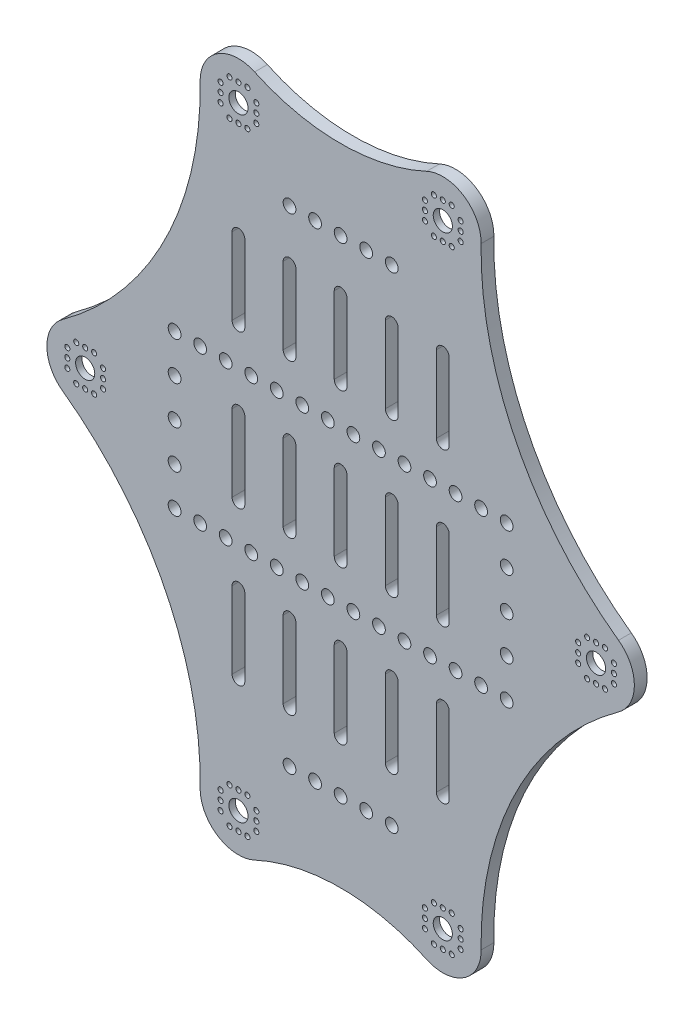
SolidWorks part; units mm, degrees
ref_plane "前视基准面" through (0, 0, 0) normal (0, 0, 1) x (1, 0, 0)
ref_plane "上视基准面" through (0, 0, 0) normal (0, 1, 0) x (1, 0, 0)
ref_plane "右视基准面" through (0, 0, 0) normal (1, 0, 0) x (0, 0, -1)
other "Configuration Table"
sketch "Sketch1" plane through (0, 0, 0) normal (0, 0, 1) x (1, 0, 0)
  line L0 (0, 0) -> (0, 120) construction
  line L1 (0, 120) -> (40, 120) construction
  line L2 (0, 0) -> (100, 0) construction
  circle A1 centre (100, 0) radius 15
  circle A2 centre (40, 120) radius 15
  circle A3 centre (-100, 0) radius 15
  circle A4 centre (-40, 120) radius 15
  circle A5 centre (40, -120) radius 15
  circle A6 centre (-40, -120) radius 15
  arc A7 (-33.6842, 133.6055) -> (33.6842, 133.6055) centre (0, 206.1684) ccw
  arc A8 (-33.6842, -133.6055) -> (33.6842, -133.6055) centre (0, -206.1684) cw
  arc A9 (-108.7909, 12.154) -> (-54.9978, 119.7403) centre (-184.9783, 117.4891) ccw
  arc A10 (108.7909, 12.154) -> (54.9978, 119.7403) centre (184.9783, 117.4891) cw
  arc A11 (108.7909, -12.154) -> (54.9978, -119.7403) centre (184.9783, -117.4891) ccw
  arc A12 (-108.7909, -12.154) -> (-54.9978, -119.7403) centre (-184.9783, -117.4891) cw
  dimension "D1" = 30
  dimension "D2" = 30
  dimension "D6" = 80
  dimension "D7" = 130
  dimension "D3" = 40
  dimension "D4" = 100
  dimension "D5" = 120
extrude "Boss-Extrude1" add sketch "Sketch1" along normal blind 5 contours A3 A12 A6 A8 A5 A11 A1 A10 A2 A7 A4 A9 | A3 | A4 | A2 | A1 | A5 | A6 A7 region at (100, 0, 0) region at (0, 0, 0) region at (40, 120, 0) region at (40, -120, 0) region at (-40, 120, 0) region at (-40, -120, 0) region at (-100, 0, 0)
sketch "Sketch2" plane through (0, 0, 0) normal (0, 0, -1) x (-1, 0, 0)
  line L0 (0, 0) -> (0, 91.5521) construction
  line L1 (0, 0) -> (39.9574, 0) construction
  circle A0 centre (-40, 120) radius 11.25
  circle A1 centre (-100, 0) radius 11.25
  circle A2 centre (100, 0) radius 11.25
  circle A3 centre (40, 120) radius 11.25
  circle A4 centre (40, -120) radius 11.25
  circle A5 centre (-40, -120) radius 11.25
  dimension "D1" = 22.5
extrude "Cut-Extrude1" cut sketch "Sketch2" against normal blind 2.5
sketch "Sketch3" plane through (0, 0, 2.5) normal (0, 0, -1) x (-1, 0, 0)
  line L0 (-40, 120) -> (-40, 127) construction
  line L1 (-40, 127) -> (-36.5, 127) construction
  line L2 (-100, 0) -> (-100, 7) construction
  line L3 (-100, 7) -> (-96.5, 7) construction
  circle A0 centre (-40, 120) radius 3.75
  circle A1 centre (-40, 127) radius 1
  circle A2 centre (-36.5, 127) radius 1
  circle A3 centre (-43.5, 127) radius 1
  circle A4 centre (-40, 120) radius 3.75
  circle A5 centre (-33, 123.5) radius 1
  circle A6 centre (-33, 120) radius 1
  circle A7 centre (-33, 116.5) radius 1
  circle A8 centre (-40, 120) radius 3.75
  circle A9 centre (-36.5, 113) radius 1
  circle A10 centre (-40, 113) radius 1
  circle A11 centre (-43.5, 113) radius 1
  circle A12 centre (-40, 120) radius 3.75
  circle A13 centre (-47, 116.5) radius 1
  circle A14 centre (-47, 120) radius 1
  circle A15 centre (-47, 123.5) radius 1
  circle A16 centre (-100, 0) radius 3.75
  circle A17 centre (-100, 7) radius 1
  circle A18 centre (-96.5, 7) radius 1
  circle A19 centre (-103.5, 7) radius 1
  circle A41 centre (-100, 0) radius 3.75
  circle A42 centre (-93, 3.5) radius 1
  circle A43 centre (-93, 0) radius 1
  circle A44 centre (-93, -3.5) radius 1
  circle A45 centre (-100, 0) radius 3.75
  circle A46 centre (-96.5, -7) radius 1
  circle A47 centre (-100, -7) radius 1
  circle A48 centre (-103.5, -7) radius 1
  circle A49 centre (-100, 0) radius 3.75
  circle A50 centre (-107, -3.5) radius 1
  circle A51 centre (-107, 0) radius 1
  circle A52 centre (-107, 3.5) radius 1
  point P33 (-40, 120)
  point P63 (-100, 0)
  dimension "D1" = 7.5
  dimension "D2" = 2
  dimension "D4" = 2
  dimension "D7" = 7.5
  dimension "D8" = 2
  dimension "D10" = 2
  dimension "D3" = 7
  dimension "D5" = 3.5
  dimension "D9" = 7
  dimension "D11" = 3.5
  dimension "D12" = 4
  dimension "D6" = 4
extrude "Cut-Extrude2" cut sketch "Sketch3" against normal blind 2.5 contours A15 | A14 | A13 | A0 | A11 | A10 | A9 | A7 | A6 | A5 | A2 | A1 | A3 | A47 | A49 | A43 | A45 | A16 | A50 | A51 | A52 | A19 | A17 | A18 | A46 | A48 | A44 | A42
mirror "Mirror1" about plane through (0, 0, 0) normal (1, 0, 0) of "Cut-Extrude2"
mirror "Mirror2" about plane through (0, 0, 0) normal (0, 1, 0) of "Cut-Extrude2", "Mirror1"
sketch "Sketch4" plane through (0, 0, 5) normal (0, 0, 1) x (1, 0, 0)
  arc A24 (-83.8778, 0) -> (-30.4292, 105.6743) centre (-184.9783, 117.4891) ccw
  arc A25 (-30.4292, -105.6743) -> (-83.8778, 0) centre (-184.9783, -117.4891) ccw
  arc A26 (30.4292, -105.6743) -> (-30.4292, -105.6743) centre (0, -206.1684) ccw
  arc A27 (83.8778, 0) -> (30.4292, -105.6743) centre (184.9783, -117.4891) ccw
  arc A28 (30.4292, 105.6743) -> (83.8778, 0) centre (184.9783, 117.4891) ccw
  arc A29 (-30.4292, 105.6743) -> (30.4292, 105.6743) centre (0, 206.1684) ccw
  arc A30 (-83.8778, 0) -> (-30.4292, 105.6743) centre (-184.9783, 117.4891) ccw
  arc A31 (-30.4292, -105.6743) -> (-83.8778, 0) centre (-184.9783, -117.4891) ccw
  arc A32 (30.4292, -105.6743) -> (-30.4292, -105.6743) centre (0, -206.1684) ccw
  arc A33 (83.8778, 0) -> (30.4292, -105.6743) centre (184.9783, -117.4891) ccw
  arc A34 (30.4292, 105.6743) -> (83.8778, 0) centre (184.9783, 117.4891) ccw
  arc A35 (-30.4292, 105.6743) -> (30.4292, 105.6743) centre (0, 206.1684) ccw
  dimension "D1" = 25
extrude "Cut-Extrude3" [suppressed] cut sketch "Sketch4" against normal through all
fillet "Fillet1" [suppressed] radius 20
sketch "Sketch5" plane through (0, 0, 0) normal (0, 0, -1) x (-1, 0, 0)
  line L0 (0, 95) -> (0, 126.1684) construction
  line L1 (0, 95) -> (20, 95) construction
  line L2 (0, -95) -> (0, -126.1684) construction
  line L3 (0, 0) -> (50.0339, 0) construction
  line L5 (0, -95) -> (20, -95) construction
  circle A0 centre (20, 95) radius 2.5
  circle A1 centre (0, 95) radius 2.5
  circle A2 centre (10, 95) radius 2.5
  circle A17 centre (10, -95) radius 2.5
  circle A18 centre (0, -95) radius 2.5
  circle A19 centre (20, -95) radius 2.5
  arc A20 (-33.6842, 133.6055) -> (33.6842, 133.6055) centre (0, 206.1684) ccw construction
  circle A21 centre (-20, 95) radius 2.5
  circle A22 centre (-10, 95) radius 2.5
  arc A23 (33.6842, -133.6055) -> (-33.6842, -133.6055) centre (0, -206.1684) ccw construction
  circle A24 centre (-20, -95) radius 2.5
  circle A25 centre (-10, -95) radius 2.5
  dimension "D1" = 5
  dimension "D2" = 5
  dimension "D4" = 5
  dimension "D3" = 95
  dimension "D5" = 10
extrude "Cut-Extrude4" cut sketch "Sketch5" against normal blind 12.5
sketch "Sketch7" [suppressed] plane through (0, 0, 0) normal (0, 0, -1) x (-1, 0, 0)
  line L0 (-142.3284, 63.1511) -> (-138.4501, 72.3684) construction
  line L1 (-66.361, 51.7375) -> (-44.32, 39.8221) construction
  line L2 (-152.9421, 69.9963) -> (-131.7148, 56.3059) construction
  line L3 (-131.7148, 56.3059) -> (-142.3284, 63.1511) construction
  line L4 (-55.3405, 45.7798) -> (-52.1848, 55.2688) construction
  circle A6 centre (-142.3284, 63.1511) radius 2.5
  circle A7 centre (-138.4501, 72.3684) radius 2.5
  circle A8 centre (-134.5717, 81.5857) radius 2.5
  circle A9 centre (-142.3284, 63.1511) radius 2.5
  circle A10 centre (-146.2068, 53.9338) radius 2.5
  circle A11 centre (-150.0851, 44.7165) radius 2.5
  arc A12 (-95.3356, 10.8708) -> (-54.9908, 100.526) centre (-184.9108, 105.0849) ccw construction
  arc A13 (-70.9715, 0) -> (-31.105, 85.8815) centre (-184.9108, 105.0849) ccw construction
  circle A14 centre (-55.3405, 45.7798) radius 2.5
  circle A15 centre (-52.1848, 55.2688) radius 2.5
  circle A16 centre (-48.3064, 64.4861) radius 2.5
  circle A17 centre (-59.2189, 36.5625) radius 2.5
  circle A18 centre (-63.0972, 27.3452) radius 2.5
  dimension "D1" = 5
  dimension "D2" = 5
  dimension "D7" = 5
  dimension "D9" = 5
  dimension "D3" = 100
  dimension "D4" = 10
  dimension "D5" = 10
  dimension "D6" = 10
  dimension "D8" = 100
  dimension "D10" = 10
  dimension "D11" = 2
extrude "Cut-Extrude5" [suppressed] cut sketch "Sketch7" against normal blind 10 contours A14 | A17 | A18 | A16 | A15
sketch "Sketch8" plane through (0, 0, 5) normal (0, 0, 1) x (1, 0, 0)
  line L0 (0, 0) -> (0, 75) construction
  line L1 (0, 75) -> (40, 75) construction
  line L2 (40, 75) -> (40, 45) construction
  line L3 (42.5, 75) -> (42.5, 45)
  line L4 (37.5, 75) -> (37.5, 45)
  line L5 (20, 75) -> (20, 45) construction
  line L6 (22.5, 75) -> (22.5, 45)
  line L7 (17.5, 75) -> (17.5, 45)
  line L8 (0, 75) -> (0, 45) construction
  line L9 (2.5, 75) -> (2.5, 45)
  line L10 (-2.5, 75) -> (-2.5, 45)
  line L11 (-20, 75) -> (-20, 45) construction
  line L12 (-17.5, 75) -> (-17.5, 45)
  line L13 (-22.5, 75) -> (-22.5, 45)
  line L14 (-40, 75) -> (-40, 45) construction
  line L15 (-37.5, 75) -> (-37.5, 45)
  line L16 (-42.5, 75) -> (-42.5, 45)
  line L17 (40, 120) -> (0, 120) construction
  line L18 (0, 15) -> (40, 15) construction
  line L19 (40, 15) -> (40, -15) construction
  line L20 (42.5, 15) -> (42.5, -15)
  line L21 (37.5, 15) -> (37.5, -15)
  line L22 (20, 15) -> (20, -15) construction
  line L23 (22.5, 15) -> (22.5, -15)
  line L24 (17.5, 15) -> (17.5, -15)
  line L25 (0, 15) -> (0, -15) construction
  line L26 (2.5, 15) -> (2.5, -15)
  line L27 (-2.5, 15) -> (-2.5, -15)
  line L28 (-20, 15) -> (-20, -15) construction
  line L29 (-17.5, 15) -> (-17.5, -15)
  line L30 (-22.5, 15) -> (-22.5, -15)
  line L31 (-40, 15) -> (-40, -15) construction
  line L32 (-37.5, 15) -> (-37.5, -15)
  line L33 (-42.5, 15) -> (-42.5, -15)
  line L34 (0, -45) -> (40, -45) construction
  line L35 (40, -45) -> (40, -75) construction
  line L36 (42.5, -45) -> (42.5, -75)
  line L37 (37.5, -45) -> (37.5, -75)
  line L38 (20, -45) -> (20, -75) construction
  line L39 (22.5, -45) -> (22.5, -75)
  line L40 (17.5, -45) -> (17.5, -75)
  line L41 (0, -45) -> (0, -75) construction
  line L42 (2.5, -45) -> (2.5, -75)
  line L43 (-2.5, -45) -> (-2.5, -75)
  line L44 (-20, -45) -> (-20, -75) construction
  line L45 (-17.5, -45) -> (-17.5, -75)
  line L46 (-22.5, -45) -> (-22.5, -75)
  line L47 (-40, -45) -> (-40, -75) construction
  line L48 (-37.5, -45) -> (-37.5, -75)
  line L49 (-42.5, -45) -> (-42.5, -75)
  arc A0 (42.5, 75) -> (37.5, 75) centre (40, 75) ccw
  arc A1 (37.5, 45) -> (42.5, 45) centre (40, 45) ccw
  arc A2 (22.5, 75) -> (17.5, 75) centre (20, 75) ccw
  arc A3 (17.5, 45) -> (22.5, 45) centre (20, 45) ccw
  arc A4 (2.5, 75) -> (-2.5, 75) centre (0, 75) ccw
  arc A5 (-2.5, 45) -> (2.5, 45) centre (0, 45) ccw
  arc A6 (-17.5, 75) -> (-22.5, 75) centre (-20, 75) ccw
  arc A7 (-22.5, 45) -> (-17.5, 45) centre (-20, 45) ccw
  arc A8 (-37.5, 75) -> (-42.5, 75) centre (-40, 75) ccw
  arc A9 (-42.5, 45) -> (-37.5, 45) centre (-40, 45) ccw
  arc A10 (42.5, 15) -> (37.5, 15) centre (40, 15) ccw
  arc A11 (37.5, -15) -> (42.5, -15) centre (40, -15) ccw
  arc A12 (22.5, 15) -> (17.5, 15) centre (20, 15) ccw
  arc A13 (17.5, -15) -> (22.5, -15) centre (20, -15) ccw
  arc A14 (2.5, 15) -> (-2.5, 15) centre (0, 15) ccw
  arc A15 (-2.5, -15) -> (2.5, -15) centre (0, -15) ccw
  arc A16 (-17.5, 15) -> (-22.5, 15) centre (-20, 15) ccw
  arc A17 (-22.5, -15) -> (-17.5, -15) centre (-20, -15) ccw
  arc A18 (-37.5, 15) -> (-42.5, 15) centre (-40, 15) ccw
  arc A19 (-42.5, -15) -> (-37.5, -15) centre (-40, -15) ccw
  arc A20 (42.5, -45) -> (37.5, -45) centre (40, -45) ccw
  arc A21 (37.5, -75) -> (42.5, -75) centre (40, -75) ccw
  arc A22 (22.5, -45) -> (17.5, -45) centre (20, -45) ccw
  arc A23 (17.5, -75) -> (22.5, -75) centre (20, -75) ccw
  arc A24 (2.5, -45) -> (-2.5, -45) centre (0, -45) ccw
  arc A25 (-2.5, -75) -> (2.5, -75) centre (0, -75) ccw
  arc A26 (-17.5, -45) -> (-22.5, -45) centre (-20, -45) ccw
  arc A27 (-22.5, -75) -> (-17.5, -75) centre (-20, -75) ccw
  arc A28 (-37.5, -45) -> (-42.5, -45) centre (-40, -45) ccw
  arc A29 (-42.5, -75) -> (-37.5, -75) centre (-40, -75) ccw
  point P3 (40, 60)
  point P11 (20, 60)
  point P18 (0, 60)
  point P25 (-20, 60)
  point P32 (-40, 60)
  point P44 (40, 0)
  point P51 (20, 0)
  point P58 (0, 0)
  point P65 (-20, 0)
  point P72 (-40, 0)
  point P80 (40, -60)
  point P87 (20, -60)
  point P94 (0, -60)
  point P101 (-20, -60)
  point P108 (-40, -60)
  dimension "D3" = 2.5
  dimension "D1" = 40
  dimension "D2" = 75
  dimension "D4" = 30
  dimension "D6" = 20
  dimension "D8" = 60
  dimension "D5" = 5
  dimension "D7" = 3
extrude "Cut-Extrude6" cut sketch "Sketch8" against normal blind 10
sketch "Sketch9" plane through (0, 0, 5) normal (0, 0, 1) x (1, 0, 0)
  line L0 (0, 0) -> (0, 30) construction
  line L1 (0, 30) -> (-65, 30) construction
  line L2 (0, 0) -> (100, 0) construction
  line L3 (0, -30) -> (-65, -30) construction
  circle A0 centre (-65, 30) radius 2.5
  circle A1 centre (-55, 30) radius 2.5
  circle A2 centre (-45, 30) radius 2.5
  circle A3 centre (-35, 30) radius 2.5
  circle A4 centre (-25, 30) radius 2.5
  circle A5 centre (-15, 30) radius 2.5
  circle A6 centre (-5, 30) radius 2.5
  circle A7 centre (5, 30) radius 2.5
  circle A8 centre (15, 30) radius 2.5
  circle A9 centre (25, 30) radius 2.5
  circle A10 centre (35, 30) radius 2.5
  circle A11 centre (45, 30) radius 2.5
  circle A12 centre (55, 30) radius 2.5
  circle A13 centre (65, 30) radius 2.5
  circle A14 centre (65, -30) radius 2.5
  circle A15 centre (55, -30) radius 2.5
  circle A16 centre (45, -30) radius 2.5
  circle A17 centre (35, -30) radius 2.5
  circle A18 centre (25, -30) radius 2.5
  circle A19 centre (15, -30) radius 2.5
  circle A20 centre (5, -30) radius 2.5
  circle A21 centre (-5, -30) radius 2.5
  circle A22 centre (-15, -30) radius 2.5
  circle A23 centre (-25, -30) radius 2.5
  circle A24 centre (-35, -30) radius 2.5
  circle A25 centre (-45, -30) radius 2.5
  circle A26 centre (-55, -30) radius 2.5
  circle A27 centre (-65, -30) radius 2.5
  dimension "D1" = 5
  dimension "D2" = 30
  dimension "D3" = 65
  dimension "D5" = 10
  dimension "D4" = 14
extrude "Cut-Extrude7" cut sketch "Sketch9" against normal blind 10
sketch "Sketch10" plane through (0, 0, 5) normal (0, 0, 1) x (1, 0, 0)
  line L0 (0, 0) -> (-65, 0) construction
  line L1 (-65, 0) -> (-40, 15) construction
  line L2 (-40, 15) -> (-65, 15) construction
  line L3 (-65, 15) -> (-65, 0) construction
  line L4 (0, 0) -> (0, 17.5) construction
  line L5 (65, -15) -> (65, -30) construction
  circle A1 centre (-65, 0) radius 2.5
  circle A2 centre (-65, 15) radius 2.5
  circle A3 centre (-65, -15) radius 2.5
  arc A4 (2.5, 15) -> (-2.5, 15) centre (0, 15) ccw construction
  circle A5 centre (65, -15) radius 2.5
  circle A6 centre (65, 0) radius 2.5
  circle A7 centre (65, 15) radius 2.5
  dimension "D1" = 5
  dimension "D3" = 5
  dimension "D2" = 65
extrude "Cut-Extrude8" cut sketch "Sketch10" against normal blind 10
sketch "Sketch11" plane through (0, 0, 5) normal (0, 0, 1) x (1, 0, 0)
  line L0 (-115, 0) -> (115, 0)
  line L1 (-115, -135) -> (115, -135)
  line L2 (-115, -135) -> (-115, 135)
  line L3 (-115, 135) -> (115, 135)
  line L4 (115, -135) -> (115, 135)
  line L5 (-115, -135) -> (115, 135) construction
  line L6 (-115, 135) -> (115, -135) construction
  point P0 (0, 0)
  dimension "D1" = 270
  dimension "D2" = 230
extrude "Cut-Extrude9" [suppressed] cut sketch "Sketch11" against normal blind 10 contours L1 L4 L0 L2
sketch "Sketch12" plane through (0, 0, 5) normal (0, 0, 1) x (1, 0, 0)
  line L0 (-20, 95) -> (20, 95) construction
